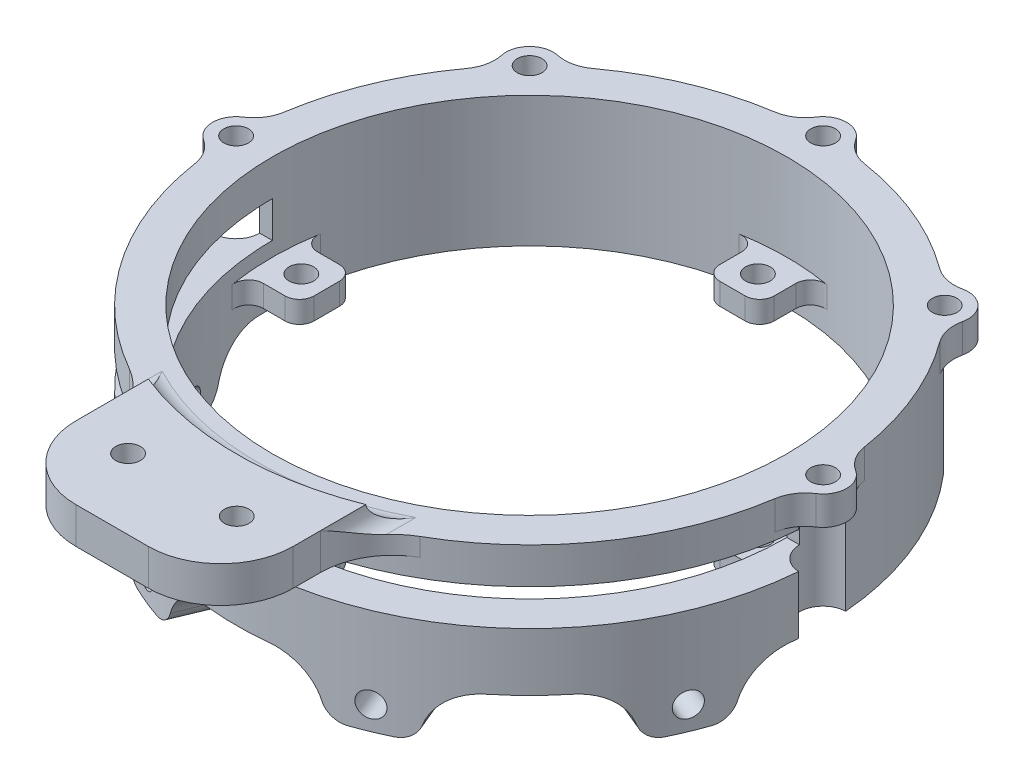
SolidWorks part; units mm, degrees
ref_plane "Alzado" through (0, 0, 0) normal (0, 0, 1) x (1, 0, 0)
ref_plane "Planta" through (0, 0, 0) normal (0, 1, 0) x (1, 0, 0)
ref_plane "Vista lateral" through (0, 0, 0) normal (1, 0, 0) x (0, 0, -1)
sketch "Croquis1" plane through (0, 0, 0) normal (0, 1, 0) x (1, 0, 0)
  circle A0 centre (0, 0) radius 35.5
  circle A1 centre (0, 0) radius 40.5
  dimension "D1" = 71
  dimension "D2" = 5
extrude "Saliente-Extruir1" add sketch "Croquis1" along normal mid plane 18
sketch "Croquis2" plane through (0, 9, 0) normal (0, -1, 0) x (1, 0, 0)
  line L0 (-15, 37.6198) -> (-15, 57.6198)
  line L1 (-15, 57.6198) -> (15, 57.6198)
  line L2 (15, 57.6198) -> (15, 37.6198)
  line L3 (0, 0) -> (0, 98.2113) construction
  circle A0 centre (0, 0) radius 40.5 construction
  arc A1 (15, 37.6198) -> (-15, 37.6198) centre (0, 0) ccw
  circle A2 centre (-7.5, 47.9166) radius 1.7
  circle A3 centre (7.5, 47.9166) radius 1.7
  circle A6 centre (0, 0) radius 48.5
  circle A7 centre (0, 0) radius 48.5 construction
  point P7 (0, 57.6198)
  dimension "D5" = 3.4
  dimension "D1" = 30
  dimension "D2" = 20
  dimension "D3" = 8
  dimension "D4" = 15
extrude "Saliente-Extruir2" add sketch "Croquis2" along normal mid plane 5
fillet "Redondeo1" radius 10 4 edges at (15, 7.75, 37.6198) (-15, 7.75, 37.6198) (-15, 9, 57.6198) (15, 9, 57.6198)
ref_plane "Plano1" through (0, -6, 0) normal (0, -1, 0) x (-1, 0, 0)
sketch "Croquis4" plane through (0, -6, 0) normal (0, -1, 0) x (-1, 0, 0)
  line L0 (0, -35.5) -> (0, 0) construction
  line L1 (-3.75, -35.3014) -> (-3.75, -28)
  line L2 (-3.75, -28) -> (3.75, -28)
  line L3 (3.75, -35.3014) -> (3.75, -28)
  circle A0 centre (0, 0) radius 35.5 construction
  arc A1 (-3.75, -35.3014) -> (3.75, -35.3014) centre (0, 0) ccw
  circle A2 centre (0, 0) radius 25 construction
  circle A3 centre (0, -31.5) radius 1.7
  circle A4 centre (0, 0) radius 31.5 construction
  point P12 (0, -28)
  dimension "D1" = 3.4
  dimension "D5" = 50
  dimension "D6" = 6.5
  dimension "D3" = 7.5
  dimension "D4" = 3.75
extrude "Saliente-Extruir3" add sketch "Croquis4" against normal blind 3
fillet "Redondeo2" radius 2 4 edges at (-3.75, -4.5, 35.3014) (3.75, -4.5, 28) (-3.75, -4.5, 28) (3.75, -4.5, 35.3014)
pattern_circular "MatrizC1" count 4 every 90 about axis through (0, 9, 0) along (0, 1, 0) of "Saliente-Extruir3", "Redondeo2"
hole_wizard "Refrentado para tornillo con cabeza plana de M31" positions "Croquis5" profile "Croquis7" counterbore size "M3" standard "ISO" end condition through all
sketch "Croquis5" plane through (0, -9, 0) normal (0, -1, 0) x (-1, 0, 0)
  circle A0 centre (0, 0) radius 40.5 construction
  point P0 (0, 40.5)
sketch "Croquis7" plane through (0, -9, -40.5) normal (1, 0, 0) x (0, 0, -1)
  line L0 (0, 0) -> (0, 20.5)
  line L1 (0, 20.5) -> (1.7, 20.5)
  line L3 (1.7, 20.5) -> (1.7, 14)
  line L4 (1.7, 14) -> (3.25, 14)
  line L5 (3.25, 14) -> (3.25, 0)
  line L7 (3.25, 0) -> (0, 0)
  line L11 (0, -6.35) -> (0, 107.95) construction
  dimension "Diámetro de taladro hasta el siguiente" = 3.4
  dimension "Profundidad de taladro hasta el siguiente" = 20.5
  dimension "Diámetro de refrentado" = 6.5
  dimension "Profundidad de refrentado" = 14
sketch "Croquis8" plane through (0, 5, 0) normal (0, -1, 0) x (1, 0, 0)
  circle A0 centre (0, -40.5) radius 3.25
  circle A2 centre (0, -40.5) radius 1.7
extrude "Saliente-Extruir4" add sketch "Croquis8" against normal up to surface (4 mm away) up to face at (0, 9, 17.7263)
pattern_circular "MatrizC2" count 3 every 45 about axis through (0, -9, 0) along (0, 1, 0) of "Saliente-Extruir4", "Refrentado para tornillo con cabeza plana de M31"
mirror "Simetría1" about plane through (0, 0, 0) normal (1, 0, 0) of "MatrizC2"
fillet "Redondeo4" radius 5 10 edges at (-40.3696, 7, -3.2474) (-40.3696, 7, 3.2474) (-30.8419, 7, -26.2494) (-26.2494, 7, -30.8419) (-3.2474, 7, -40.3696) (3.2474, 7, -40.3696) (40.3696, 7, -3.2474) (40.3696, 7, 3.2474) (30.8419, 7, -26.2494) (26.2494, 7, -30.8419)
sketch "Croquis9" plane through (0, -9, 0) normal (0, -1, 0) x (1, 0, 0)
  line L0 (0, 0) -> (29.1912, 12.0914) construction
  line L2 (-16.8451, 0) -> (16.8451, 0) construction
  line L3 (39.0443, 10.7607) -> (34.3842, 8.8304)
  line L5 (35.2175, 19.9995) -> (30.5574, 18.0692)
  arc A9 (-40.3696, -3.2474) -> (-30.8419, -26.2494) centre (0, 0) ccw construction
  arc A10 (39.0443, 10.7607) -> (35.2175, 19.9995) centre (0, 0) ccw
  circle A11 centre (0, 0) radius 35.5 construction
  arc A12 (34.3842, 8.8304) -> (30.5574, 18.0692) centre (0, 0) ccw
  point P4 (0, 0)
  dimension "D1" = 202.5
  dimension "D2" = 10
extrude "Saliente-Extruir5" add sketch "Croquis9" along normal blind 6.5
ref_plane "Plano2" through (37.4171, 0, 15.4987) normal (0.9239, 0, 0.3827) x (0.3827, 0, -0.9239)
sketch "Croquis10" plane through (37.4171, 0, 15.4987) normal (0.9239, 0, 0.3827) x (0.3827, 0, -0.9239)
  line L0 (-5, -12.25) -> (5, -12.25) construction
  line L1 (-5, -15.5) -> (-5, -9) construction
  line L2 (5, -15.5) -> (5, -9) construction
  circle A0 centre (0, -12.25) radius 1.7
  point P9 (0, -12.25)
  dimension "D1" = 3.4
extrude "Cortar-Extruir2" cut sketch "Croquis10" against normal up to surface (5.0407 mm away) up to face at (0, 9, 35.5)
pattern_circular "MatrizC3" count 4 every 45 about axis through (0, -9, 0) along (0, 1, 0) of "Saliente-Extruir5", "Cortar-Extruir2" reverse direction yes
fillet "Redondeo5" radius 6.5 8 edges at (9.7956, -9, 36.7142) (19.0344, -9, 32.8874) (32.8874, -9, 19.0344) (36.7142, -9, 9.7956) (-36.7142, -9, 9.7956) (-32.8874, -9, 19.0344) (-19.0344, -9, 32.8874) (-9.7956, -9, 36.7142)
fillet "Redondeo6" radius 3 8 edges at (-36.7142, -15.5, 9.7956) (-32.8874, -15.5, 19.0344) (19.0344, -15.5, 32.8874) (9.7956, -15.5, 36.7142) (-9.7956, -15.5, 36.7142) (-19.0344, -15.5, 32.8874) (36.7142, -15.5, 9.7956) (32.8874, -15.5, 19.0344)
fillet "Redondeo7" radius 3 1 edges at (0, 9, 40.5)
fillet "Redondeo8" radius 2.5 2 edges at (15, 9, 39.1464) (-15, 9, 39.1464)
sketch "Croquis11" plane through (0, 0, 0) normal (0, 0, 1) x (1, 0, 0)
  line L1 (-40.5, 4) -> (40.5, 4)
  line L2 (-40.5, 4) -> (-40.5, -1)
  line L3 (-40.5, -1) -> (40.5, -1)
  line L4 (40.5, 4) -> (40.5, -1)
  line L5 (-40.5, 4) -> (40.5, -1) construction
  line L6 (-40.5, -1) -> (40.5, 4) construction
  line L8 (-20.0495, 9) -> (-40.0268, 9) construction
  point P0 (0, 0)
  point P8 (0, 0)
  point P9 (0, 0)
  dimension "D1" = 5
  dimension "D2" = 81
  dimension "D3" = 5
extrude "Cortar-Extruir3" cut sketch "Croquis11" along normal blind 47
